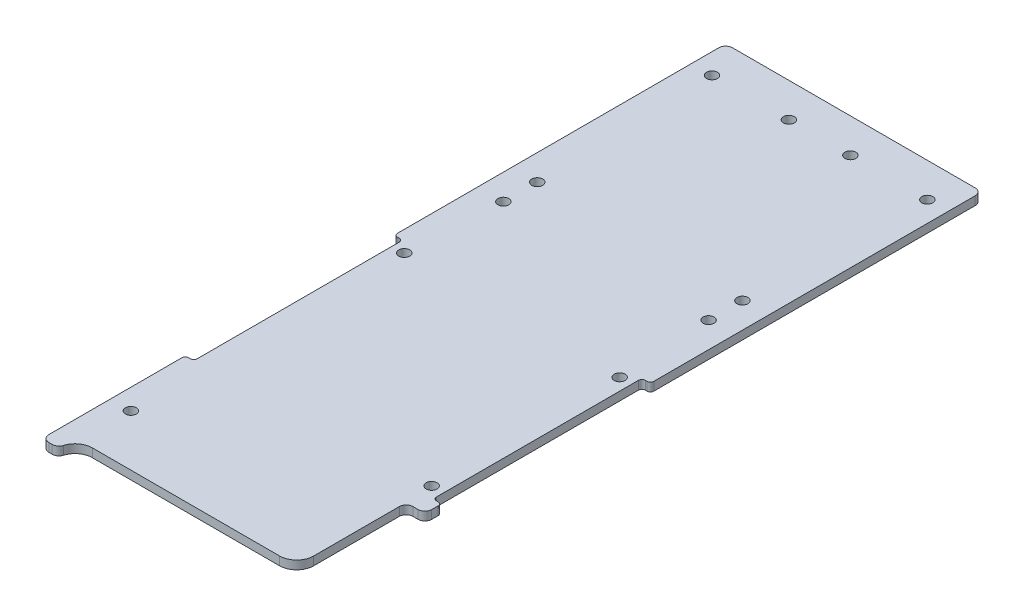
SolidWorks part; units mm, degrees
ref_plane "Front Plane" through (0, 0, 0) normal (0, 0, 1) x (1, 0, 0)
ref_plane "Top Plane" through (0, 0, 0) normal (0, 1, 0) x (1, 0, 0)
ref_plane "Right Plane" through (0, 0, 0) normal (1, 0, 0) x (0, 0, -1)
sketch "Sketch1" plane through (0, 0, 0) normal (0, 1, 0) x (1, 0, 0)
  line L0 (-39.9997, 0) -> (-39.9997, 114.3) construction
  line L1 (-47.625, 127) -> (47.625, 127)
  line L2 (-47.625, 127) -> (-47.625, -127)
  line L3 (-47.625, -127) -> (47.625, -127)
  line L4 (47.625, 127) -> (47.625, -127)
  line L5 (-47.625, 127) -> (47.625, -127) construction
  line L6 (-47.625, -127) -> (47.625, 127) construction
  line L7 (0, 0) -> (0, 127) construction
  line L8 (-39.9997, 0) -> (-39.9997, -101.6) construction
  line L9 (-39.9997, 0) -> (0, 0) construction
  line L10 (-41.275, -127) -> (-41.275, -120.65)
  line L11 (-41.275, -120.65) -> (41.275, -120.65)
  line L12 (41.275, -120.65) -> (41.275, -127)
  line L13 (-39.9997, 114.3) -> (-11.4247, 114.3) construction
  line L14 (39.9997, 114.3) -> (11.4247, 114.3) construction
  circle A0 centre (-39.9997, 114.3) radius 2.032
  circle A1 centre (-39.9997, 0) radius 2.032
  circle A2 centre (-39.9997, -101.6) radius 2.032
  circle A3 centre (39.9997, -101.6) radius 2.032
  circle A4 centre (39.9997, 0) radius 2.032
  circle A5 centre (39.9997, 114.3) radius 2.032
  circle A6 centre (-11.4247, 114.3) radius 2.032
  circle A7 centre (11.4247, 114.3) radius 2.032
  circle A8 centre (-39.9997, -69.85) radius 2.032
  circle A9 centre (39.9997, -69.85) radius 2.032
  point P0 (0, 0)
  dimension "D4" = 4.064
  dimension "D10" = 28.575
  dimension "D1" = 95.25
  dimension "D2" = 254
  dimension "D3" = 7.6253
  dimension "D5" = 12.7
  dimension "D6" = 25.4
  dimension "D7" = 6.35
  dimension "D8" = 6.35
  dimension "D9" = 6.35
  dimension "D11" = 69.85
extrude "Boss-Extrude1" add sketch "Sketch1" along normal blind 3.175 contours L4 L1 L2 L3 A4 A0 A1 A2 A3 A5 | A8 | A3 region at (0, 0, -2.6944) region at (39.9997, 0, 101.6) region at (-39.9997, 0, 69.85)
fillet "Fillet1" radius 2.54 4 edges at (-47.625, 1.5875, -127) (47.625, 1.5875, -127) (47.625, 1.5875, 127) (-47.625, 1.5875, 127)
fillet "Fillet2" radius 2.54 2 edges at (41.275, 1.5875, 127) (-41.275, 1.5875, 127)
fillet "Fillet3" radius 6.35 2 edges at (41.275, 1.5875, 120.65) (-41.275, 1.5875, 120.65)
sketch "Sketch2" plane through (0, 0, 0) normal (0, -1, 0) x (1, 0, 0)
  line L0 (41.9113, 131.8831) -> (41.9113, 109.8659) construction
  line L1 (41.9113, 109.8659) -> (41.9113, 106.3879) construction
  line L2 (41.9113, 83.271) -> (41.9113, 82.5325) construction
  line L3 (41.9113, 82.5325) -> (41.9113, 81.2514) construction
  line L4 (41.9113, 83.271) -> (41.9113, 106.3879) construction
  line L5 (41.9113, 131.8831) -> (41.9113, 109.8659)
  line L6 (41.9113, 109.8659) -> (41.9113, 106.3879)
  line L7 (41.9113, 83.271) -> (41.9113, 82.5325)
  line L8 (41.9113, 82.5325) -> (41.9113, 81.2514)
  line L9 (41.9113, 83.271) -> (41.9113, 106.3879)
  line L10 (41.9113, 81.2514) -> (47.625, 81.2514)
  line L11 (47.625, -124.46) -> (47.625, 124.46) construction
  line L12 (41.9113, 131.8831) -> (47.625, 131.8831)
  line L13 (47.625, 131.8831) -> (47.625, 81.2514)
  line L14 (40.6413, 79.9814) -> (48.895, 79.9814)
  line L15 (48.895, 133.1531) -> (48.895, 79.9814)
  line L16 (40.6413, 133.1531) -> (48.895, 133.1531)
  line L17 (40.6413, 133.1531) -> (40.6413, 109.8659)
  line L18 (40.6413, 109.8659) -> (40.6413, 106.3879)
  line L19 (40.6413, 83.271) -> (40.6413, 106.3879)
  line L20 (40.6413, 83.271) -> (40.6413, 82.5325)
  line L21 (40.6413, 82.5325) -> (40.6413, 79.9814)
  arc M7 (43.815, 127) -> (41.3809, 125.1857) centre (43.815, 124.46) ccw
  arc M8 (41.3809, 125.1857) -> (35.2956, 120.65) centre (35.2956, 127) cw
  line M18 (47.625, -124.46) -> (47.625, 124.46)
  dimension "D1" = 1.27
extrude "Cut-Extrude1" cut sketch "Sketch2" against normal through all contours L20 L21 L14 L10 L8 L7 L9 L19 M18 | L19 L9 L6 L5 L17 L18 M7 M8 | L13 L10 L8 L7 L9 L6 L5 L12 region at (41.6763, 0, 99.9805)
fillet "Fillet4" radius 6.35 1 edges at (40.6413, 1.5875, 123.5728)
fillet "Fillet5" radius 2.54 2 edges at (47.625, 1.5875, 79.9814) (40.6413, 1.5875, 79.9814)
sketch "Sketch3" plane through (0, 0, 0) normal (0, -1, 0) x (1, 0, 0)
  line L0 (-36.3092, -49.7791) -> (-39.916, -49.7791) construction
  line L1 (-40.424, -49.276) -> (-40.424, -45.7043) construction
  line L2 (-35.8012, -45.7043) -> (-35.8012, -49.276) construction
  line L3 (-39.916, -45.2013) -> (-36.3092, -45.2013) construction
  line L4 (-36.3092, -37.2027) -> (-39.916, -37.2027) construction
  line L5 (-35.8012, -33.1279) -> (-35.8012, -36.6996) construction
  line L6 (-40.424, -36.6996) -> (-40.424, -33.1279) construction
  line L7 (-39.916, -32.6249) -> (-36.3092, -32.6249) construction
  line L8 (36.284, -32.6249) -> (39.8908, -32.6249) construction
  line L9 (40.3988, -33.1279) -> (40.3988, -36.6996) construction
  line L10 (39.8908, -37.2027) -> (36.284, -37.2027) construction
  line L11 (35.776, -36.6996) -> (35.776, -33.1279) construction
  line L12 (36.284, -45.2013) -> (39.8908, -45.2013) construction
  line L13 (35.776, -49.276) -> (35.776, -45.7043) construction
  line L14 (40.3988, -45.7043) -> (40.3988, -49.276) construction
  line L15 (39.8908, -49.7791) -> (36.284, -49.7791) construction
  line L16 (-36.3092, -49.7791) -> (-39.916, -49.7791)
  line L17 (-40.424, -49.276) -> (-40.424, -45.7043)
  line L18 (-35.8012, -45.7043) -> (-35.8012, -49.276)
  line L19 (-39.916, -45.2013) -> (-36.3092, -45.2013)
  line L20 (-36.3092, -37.2027) -> (-39.916, -37.2027)
  line L21 (-35.8012, -33.1279) -> (-35.8012, -36.6996)
  line L22 (-40.424, -36.6996) -> (-40.424, -33.1279)
  line L23 (-39.916, -32.6249) -> (-36.3092, -32.6249)
  line L24 (36.284, -32.6249) -> (39.8908, -32.6249)
  line L25 (40.3988, -33.1279) -> (40.3988, -36.6996)
  line L26 (39.8908, -37.2027) -> (36.284, -37.2027)
  line L27 (35.776, -36.6996) -> (35.776, -33.1279)
  line L28 (36.284, -45.2013) -> (39.8908, -45.2013)
  line L29 (35.776, -49.276) -> (35.776, -45.7043)
  line L30 (40.3988, -45.7043) -> (40.3988, -49.276)
  line L31 (39.8908, -49.7791) -> (36.284, -49.7791)
  line L32 (-47.625, -25.836) -> (47.625, -25.836)
  line L33 (-47.625, -124.46) -> (-47.625, 124.46) construction
  line L34 (47.625, -124.46) -> (47.625, 77.4414) construction
  line L35 (0, -25.836) -> (0, -56.0686) construction
  line L38 (134.3616, -51.414) -> (184.1374, -51.414)
  line L39 (184.1374, -51.414) -> (184.1374, -43.4909)
  line L40 (184.1374, -43.4909) -> (182.334, -43.4909)
  line L41 (181.826, -42.9878) -> (181.826, -39.4161)
  line L42 (182.334, -38.9131) -> (184.1374, -38.9131)
  line L43 (184.1374, -38.9131) -> (184.1374, -30.9899)
  line L44 (184.1374, -30.9899) -> (134.3616, -30.9899)
  line L45 (134.3616, -30.9899) -> (133.3374, -32.0042)
  line L46 (133.3374, -32.0042) -> (132.3132, -30.9899)
  line L47 (132.3132, -30.9899) -> (70.8616, -30.9899)
  line L48 (70.8616, -30.9899) -> (69.8374, -32.0042)
  line L49 (69.8374, -32.0042) -> (68.8132, -30.9899)
  line L50 (68.8132, -30.9899) -> (7.3616, -30.9899)
  line L51 (7.3616, -30.9899) -> (6.3374, -32.0042)
  line L52 (6.3374, -32.0042) -> (5.3132, -30.9899)
  line L53 (5.3132, -30.9899) -> (-56.1384, -30.9899)
  line L54 (-56.1384, -30.9899) -> (-57.1626, -32.0042)
  line L55 (-57.1626, -32.0042) -> (-58.1868, -30.9899)
  line L56 (-58.1868, -30.9899) -> (-119.6384, -30.9899)
  line L57 (-119.6384, -30.9899) -> (-120.6626, -32.0042)
  line L58 (-120.6626, -32.0042) -> (-121.6868, -30.9899)
  line L59 (-121.6868, -30.9899) -> (-184.1626, -30.9899)
  line L60 (-184.1626, -30.9899) -> (-184.1626, -51.414)
  line L61 (-184.1626, -51.414) -> (-121.6868, -51.414)
  line L62 (-121.6868, -51.414) -> (-120.6626, -50.3998)
  line L63 (-120.6626, -50.3998) -> (-119.6384, -51.414)
  line L64 (-119.6384, -51.414) -> (-58.1868, -51.414)
  line L65 (-58.1868, -51.414) -> (-57.1626, -50.3998)
  line L66 (-57.1626, -50.3998) -> (-56.1384, -51.414)
  line L67 (-56.1384, -51.414) -> (5.3132, -51.414)
  line L68 (5.3132, -51.414) -> (6.3374, -50.3998)
  line L69 (6.3374, -50.3998) -> (7.3616, -51.414)
  line L70 (7.3616, -51.414) -> (68.8132, -51.414)
  line L71 (68.8132, -51.414) -> (69.8374, -50.3998)
  line L72 (69.8374, -50.3998) -> (70.8616, -51.414)
  line L73 (70.8616, -51.414) -> (132.3132, -51.414)
  line L74 (132.3132, -51.414) -> (133.3374, -50.3998)
  line L75 (133.3374, -50.3998) -> (134.3616, -51.414)
  line L76 (134.3616, -51.414) -> (184.1374, -51.414)
  line L77 (184.1374, -51.414) -> (184.1374, -43.4909)
  line L78 (184.1374, -43.4909) -> (182.334, -43.4909)
  line L79 (181.826, -42.9878) -> (181.826, -39.4161)
  line L80 (182.334, -38.9131) -> (184.1374, -38.9131)
  line L81 (184.1374, -38.9131) -> (184.1374, -30.9899)
  line L82 (184.1374, -30.9899) -> (134.3616, -30.9899)
  line L83 (134.3616, -30.9899) -> (133.3374, -32.0042)
  line L84 (133.3374, -32.0042) -> (132.3132, -30.9899)
  line L85 (132.3132, -30.9899) -> (70.8616, -30.9899)
  line L86 (70.8616, -30.9899) -> (69.8374, -32.0042)
  line L87 (69.8374, -32.0042) -> (68.8132, -30.9899)
  line L88 (68.8132, -30.9899) -> (7.3616, -30.9899)
  line L89 (7.3616, -30.9899) -> (6.3374, -32.0042)
  line L90 (6.3374, -32.0042) -> (5.3132, -30.9899)
  line L91 (5.3132, -30.9899) -> (-56.1384, -30.9899)
  line L92 (-56.1384, -30.9899) -> (-57.1626, -32.0042)
  line L93 (-57.1626, -32.0042) -> (-58.1868, -30.9899)
  line L94 (-58.1868, -30.9899) -> (-119.6384, -30.9899)
  line L95 (-119.6384, -30.9899) -> (-120.6626, -32.0042)
  line L96 (-120.6626, -32.0042) -> (-121.6868, -30.9899)
  line L97 (-121.6868, -30.9899) -> (-184.1626, -30.9899)
  line L98 (-184.1626, -30.9899) -> (-184.1626, -51.414)
  line L99 (-184.1626, -51.414) -> (-121.6868, -51.414)
  line L100 (-121.6868, -51.414) -> (-120.6626, -50.3998)
  line L101 (-120.6626, -50.3998) -> (-119.6384, -51.414)
  line L102 (-119.6384, -51.414) -> (-58.1868, -51.414)
  line L103 (-58.1868, -51.414) -> (-57.1626, -50.3998)
  line L104 (-57.1626, -50.3998) -> (-56.1384, -51.414)
  line L105 (-56.1384, -51.414) -> (5.3132, -51.414)
  line L106 (5.3132, -51.414) -> (6.3374, -50.3998)
  line L107 (6.3374, -50.3998) -> (7.3616, -51.414)
  line L108 (7.3616, -51.414) -> (68.8132, -51.414)
  line L109 (68.8132, -51.414) -> (69.8374, -50.3998)
  line L110 (69.8374, -50.3998) -> (70.8616, -51.414)
  line L111 (70.8616, -51.414) -> (132.3132, -51.414)
  line L112 (132.3132, -51.414) -> (133.3374, -50.3998)
  line L113 (133.3374, -50.3998) -> (134.3616, -51.414)
  line L1362 (-40.424, -34.9138) -> (-35.8012, -34.9138)
  line L1857 (-38.1126, -32.6249) -> (-38.1126, -37.2027)
  line L1858 (-38.1126, -45.2013) -> (-38.1126, -49.7791)
  line L1859 (-40.424, -47.4902) -> (-35.8012, -47.4902)
  circle A0 centre (-38.1126, -34.9138) radius 2.032
  circle A1 centre (-38.1126, -47.4902) radius 2.032
  circle A2 centre (38.1126, -47.4902) radius 2.032
  circle A3 centre (38.1126, -34.9138) radius 2.032
  ellipse E0 centre (-39.916, -45.7043) end of major axis (-39.408, -45.7043) minor radius 0.5031 (-39.916, -45.2013) -> (-40.424, -45.7043) ccw construction
  ellipse E1 centre (-39.916, -49.276) end of major axis (-39.408, -49.276) minor radius 0.5031 (-40.424, -49.276) -> (-39.916, -49.7791) ccw construction
  ellipse E2 centre (182.334, -42.9878) end of major axis (182.842, -42.9878) minor radius 0.5031 (181.826, -42.9878) -> (182.334, -43.4909) ccw
  ellipse E3 centre (182.334, -39.4161) end of major axis (182.842, -39.4161) minor radius 0.5031 (182.334, -38.9131) -> (181.826, -39.4161) ccw
  ellipse E4 centre (182.334, -42.9878) end of major axis (182.842, -42.9878) minor radius 0.5031 (181.826, -42.9878) -> (182.334, -43.4909) ccw
  ellipse E5 centre (182.334, -39.4161) end of major axis (182.842, -39.4161) minor radius 0.5031 (182.334, -38.9131) -> (181.826, -39.4161) ccw
  ellipse E6 centre (-36.3092, -49.276) end of major axis (-35.8012, -49.276) minor radius 0.5031 (-36.3092, -49.7791) -> (-35.8012, -49.276) ccw construction
  ellipse E7 centre (-36.3092, -45.7043) end of major axis (-35.8012, -45.7043) minor radius 0.5031 (-35.8012, -45.7043) -> (-36.3092, -45.2013) ccw construction
  ellipse E8 centre (-39.916, -36.6996) end of major axis (-39.408, -36.6996) minor radius 0.5031 (-40.424, -36.6996) -> (-39.916, -37.2027) ccw construction
  ellipse E9 centre (-36.3092, -36.6996) end of major axis (-35.8012, -36.6996) minor radius 0.5031 (-36.3092, -37.2027) -> (-35.8012, -36.6996) ccw construction
  ellipse E10 centre (-36.3092, -33.1279) end of major axis (-35.8012, -33.1279) minor radius 0.5031 (-35.8012, -33.1279) -> (-36.3092, -32.6249) ccw construction
  ellipse E11 centre (-39.916, -33.1279) end of major axis (-39.408, -33.1279) minor radius 0.5031 (-39.916, -32.6249) -> (-40.424, -33.1279) ccw construction
  ellipse E12 centre (39.8908, -33.1279) end of major axis (40.3988, -33.1279) minor radius 0.5031 (40.3988, -33.1279) -> (39.8908, -32.6249) ccw construction
  ellipse E13 centre (36.284, -33.1279) end of major axis (36.792, -33.1279) minor radius 0.5031 (36.284, -32.6249) -> (35.776, -33.1279) ccw construction
  ellipse E14 centre (39.8908, -36.6996) end of major axis (40.3988, -36.6996) minor radius 0.5031 (39.8908, -37.2027) -> (40.3988, -36.6996) ccw construction
  ellipse E15 centre (36.284, -36.6996) end of major axis (36.792, -36.6996) minor radius 0.5031 (35.776, -36.6996) -> (36.284, -37.2027) ccw construction
  ellipse E16 centre (36.284, -45.7043) end of major axis (36.792, -45.7043) minor radius 0.5031 (36.284, -45.2013) -> (35.776, -45.7043) ccw construction
  ellipse E17 centre (36.284, -49.276) end of major axis (36.792, -49.276) minor radius 0.5031 (35.776, -49.276) -> (36.284, -49.7791) ccw construction
  ellipse E18 centre (39.8908, -45.7043) end of major axis (40.3988, -45.7043) minor radius 0.5031 (40.3988, -45.7043) -> (39.8908, -45.2013) ccw construction
  ellipse E19 centre (39.8908, -49.276) end of major axis (40.3988, -49.276) minor radius 0.5031 (39.8908, -49.7791) -> (40.3988, -49.276) ccw construction
  ellipse E20 centre (-39.916, -45.7043) end of major axis (-39.408, -45.7043) minor radius 0.5031 (-39.916, -45.2013) -> (-40.424, -45.7043) ccw
  ellipse E21 centre (-39.916, -49.276) end of major axis (-39.408, -49.276) minor radius 0.5031 (-40.424, -49.276) -> (-39.916, -49.7791) ccw
  ellipse E22 centre (-36.3092, -49.276) end of major axis (-35.8012, -49.276) minor radius 0.5031 (-36.3092, -49.7791) -> (-35.8012, -49.276) ccw
  ellipse E23 centre (-36.3092, -45.7043) end of major axis (-35.8012, -45.7043) minor radius 0.5031 (-35.8012, -45.7043) -> (-36.3092, -45.2013) ccw
  ellipse E24 centre (-39.916, -36.6996) end of major axis (-39.408, -36.6996) minor radius 0.5031 (-40.424, -36.6996) -> (-39.916, -37.2027) ccw
  ellipse E25 centre (-36.3092, -36.6996) end of major axis (-35.8012, -36.6996) minor radius 0.5031 (-36.3092, -37.2027) -> (-35.8012, -36.6996) ccw
  ellipse E26 centre (-36.3092, -33.1279) end of major axis (-35.8012, -33.1279) minor radius 0.5031 (-35.8012, -33.1279) -> (-36.3092, -32.6249) ccw
  ellipse E27 centre (-39.916, -33.1279) end of major axis (-39.408, -33.1279) minor radius 0.5031 (-39.916, -32.6249) -> (-40.424, -33.1279) ccw
  ellipse E28 centre (39.8908, -33.1279) end of major axis (40.3988, -33.1279) minor radius 0.5031 (40.3988, -33.1279) -> (39.8908, -32.6249) ccw
  ellipse E29 centre (36.284, -33.1279) end of major axis (36.792, -33.1279) minor radius 0.5031 (36.284, -32.6249) -> (35.776, -33.1279) ccw
  ellipse E30 centre (39.8908, -36.6996) end of major axis (40.3988, -36.6996) minor radius 0.5031 (39.8908, -37.2027) -> (40.3988, -36.6996) ccw
  ellipse E31 centre (36.284, -36.6996) end of major axis (36.792, -36.6996) minor radius 0.5031 (35.776, -36.6996) -> (36.284, -37.2027) ccw
  ellipse E32 centre (36.284, -45.7043) end of major axis (36.792, -45.7043) minor radius 0.5031 (36.284, -45.2013) -> (35.776, -45.7043) ccw
  ellipse E33 centre (36.284, -49.276) end of major axis (36.792, -49.276) minor radius 0.5031 (35.776, -49.276) -> (36.284, -49.7791) ccw
  ellipse E34 centre (39.8908, -45.7043) end of major axis (40.3988, -45.7043) minor radius 0.5031 (40.3988, -45.7043) -> (39.8908, -45.2013) ccw
  ellipse E35 centre (39.8908, -49.276) end of major axis (40.3988, -49.276) minor radius 0.5031 (39.8908, -49.7791) -> (40.3988, -49.276) ccw
  dimension "D2" = 4.064
  dimension "D1" = 0
extrude "Cut-Extrude2" cut sketch "Sketch3" against normal through all contours A0 | A1 | A2 | A3
sketch "Sketch4" plane through (0, 3.175, 0) normal (0, 1, 0) x (1, 0, 0)
  line L0 (-44.45, 3.81) -> (-46.99, 3.81) construction
  line L1 (-46.99, 3.81) -> (-46.99, 121.92) construction
  line L2 (-42.545, 126.365) -> (-0.635, 126.365) construction
  line L3 (-0.635, 126.365) -> (-0.635, 107.95) construction
  line L4 (-6.35, 102.235) -> (-15.875, 102.235) construction
  line L5 (-22.86, 95.25) -> (-22.86, -115.57) construction
  line L6 (-27.305, -120.015) -> (-35.4551, -120.015) construction
  line L7 (-43.815, -126.365) -> (-45.085, -126.365) construction
  line L8 (-46.99, -124.46) -> (-46.99, -73.7819) construction
  line L9 (-46.99, -73.7819) -> (-44.45, -73.7819) construction
  line L10 (-44.45, -73.7819) -> (-44.45, 3.81) construction
  line L11 (-46.99, 3.81) -> (-44.45, 3.81)
  line L12 (-46.99, 121.92) -> (-46.99, 3.81)
  line L13 (-0.635, 126.365) -> (-42.545, 126.365)
  line L14 (-0.635, 107.95) -> (-0.635, 126.365)
  line L15 (-15.875, 102.235) -> (-6.35, 102.235)
  line L16 (-22.86, -115.57) -> (-22.86, 95.25)
  line L17 (-35.4551, -120.015) -> (-27.305, -120.015)
  line L18 (-45.085, -126.365) -> (-43.815, -126.365)
  line L19 (-46.99, -73.7819) -> (-46.99, -124.46)
  line L20 (-44.45, -73.7819) -> (-46.99, -73.7819)
  line L21 (-44.45, 3.81) -> (-44.45, -73.7819)
  line L22 (-46.99, 3.81) -> (-44.45, 3.81)
  line L23 (-46.99, 121.92) -> (-46.99, 3.81)
  line L24 (-0.635, 126.365) -> (-42.545, 126.365)
  line L25 (-0.635, 107.95) -> (-0.635, 126.365)
  line L26 (-15.875, 102.235) -> (-6.35, 102.235)
  line L27 (-22.86, -115.57) -> (-22.86, 95.25)
  line L28 (-35.4551, -120.015) -> (-27.305, -120.015)
  line L29 (-45.085, -126.365) -> (-43.815, -126.365)
  line L30 (-46.99, -73.7819) -> (-46.99, -124.46)
  line L31 (-44.45, -73.7819) -> (-46.99, -73.7819)
  line L32 (-44.45, 3.81) -> (-44.45, -73.7819)
  line L33 (40.64, -77.5286) -> (40.64, -117.0408) construction
  line L34 (35.4551, -120.015) -> (27.305, -120.015) construction
  line L35 (22.86, -115.57) -> (22.86, 95.25) construction
  line L36 (15.875, 102.235) -> (6.35, 102.235) construction
  line L37 (0.635, 107.95) -> (0.635, 126.365) construction
  line L38 (0.635, 126.365) -> (42.545, 126.365) construction
  line L39 (46.99, 121.92) -> (46.99, 3.81) construction
  line L40 (46.99, 3.81) -> (44.45, 3.81) construction
  line L41 (44.45, 3.81) -> (44.45, -73.7819) construction
  line L42 (44.45, -73.7819) -> (46.99, -73.7819) construction
  line L43 (46.99, -73.7819) -> (46.99, -77.5286) construction
  line L44 (46.99, -77.5286) -> (40.64, -77.5286) construction
  line L45 (-44.45, 3.81) -> (-46.99, 3.81)
  line L46 (-46.99, 3.81) -> (-46.99, 121.92)
  line L47 (-42.545, 126.365) -> (-0.635, 126.365)
  line L48 (-0.635, 126.365) -> (-0.635, 107.95)
  line L49 (-6.35, 102.235) -> (-15.875, 102.235)
  line L50 (-22.86, 95.25) -> (-22.86, -115.57)
  line L51 (-27.305, -120.015) -> (-35.4551, -120.015)
  line L52 (-43.815, -126.365) -> (-45.085, -126.365)
  line L53 (-46.99, -124.46) -> (-46.99, -73.7819)
  line L54 (-46.99, -73.7819) -> (-44.45, -73.7819)
  line L55 (-44.45, -73.7819) -> (-44.45, 3.81)
  line L56 (40.64, -77.5286) -> (40.64, -117.0408)
  line L57 (35.4551, -120.015) -> (27.305, -120.015)
  line L58 (22.86, -115.57) -> (22.86, 95.25)
  line L59 (15.875, 102.235) -> (6.35, 102.235)
  line L60 (0.635, 107.95) -> (0.635, 126.365)
  line L61 (0.635, 126.365) -> (42.545, 126.365)
  line L62 (46.99, 121.92) -> (46.99, 3.81)
  line L63 (46.99, 3.81) -> (44.45, 3.81)
  line L64 (44.45, 3.81) -> (44.45, -73.7819)
  line L65 (44.45, -73.7819) -> (46.99, -73.7819)
  line L66 (46.99, -73.7819) -> (46.99, -77.5286)
  line L67 (46.99, -77.5286) -> (40.64, -77.5286)
  line L178 (-46.99, 3.81) -> (-47.625, 3.81)
  line L179 (-47.625, 124.46) -> (-47.625, -124.46) construction
  line L180 (-46.99, -73.7819) -> (-47.625, -73.7819)
  line L181 (46.99, -73.7819) -> (47.625, -73.7819)
  line L182 (47.625, 124.46) -> (47.625, -77.4414) construction
  line L183 (46.99, 3.81) -> (47.625, 3.81)
  arc A0 (-42.545, 126.365) -> (-46.99, 121.92) centre (-42.545, 121.92) ccw construction
  arc A1 (-6.35, 102.235) -> (-0.635, 107.95) centre (-6.35, 107.95) ccw construction
  arc A2 (-15.875, 102.235) -> (-22.86, 95.25) centre (-15.875, 95.25) ccw construction
  arc A3 (-27.305, -120.015) -> (-22.86, -115.57) centre (-27.305, -115.57) ccw construction
  arc A4 (-35.4551, -120.015) -> (-41.9138, -124.3399) centre (-35.4551, -127) ccw construction
  arc A5 (-43.815, -126.365) -> (-41.9138, -124.3399) centre (-43.815, -124.46) ccw construction
  arc A6 (-46.99, -124.46) -> (-45.085, -126.365) centre (-45.085, -124.46) ccw construction
  arc A7 (-42.545, 126.365) -> (-46.99, 121.92) centre (-42.545, 121.92) ccw
  arc A8 (-6.35, 102.235) -> (-0.635, 107.95) centre (-6.35, 107.95) ccw
  arc A9 (-15.875, 102.235) -> (-22.86, 95.25) centre (-15.875, 95.25) ccw
  arc A10 (-27.305, -120.015) -> (-22.86, -115.57) centre (-27.305, -115.57) ccw
  arc A11 (-35.4551, -120.015) -> (-41.9138, -124.3399) centre (-35.4551, -127) ccw
  arc A12 (-43.815, -126.365) -> (-41.9138, -124.3399) centre (-43.815, -124.46) ccw
  arc A13 (-46.99, -124.46) -> (-45.085, -126.365) centre (-45.085, -124.46) ccw
  arc A14 (-42.545, 126.365) -> (-46.99, 121.92) centre (-42.545, 121.92) ccw
  arc A15 (-6.35, 102.235) -> (-0.635, 107.95) centre (-6.35, 107.95) ccw
  arc A16 (-15.875, 102.235) -> (-22.86, 95.25) centre (-15.875, 95.25) ccw
  arc A17 (-27.305, -120.015) -> (-22.86, -115.57) centre (-27.305, -115.57) ccw
  arc A18 (-35.4551, -120.015) -> (-41.9138, -124.3399) centre (-35.4551, -127) ccw
  arc A19 (-43.815, -126.365) -> (-41.9138, -124.3399) centre (-43.815, -124.46) ccw
  arc A20 (-46.99, -124.46) -> (-45.085, -126.365) centre (-45.085, -124.46) ccw
  arc A21 (36.8369, -120.153) -> (40.64, -117.0408) centre (37.465, -117.0408) ccw construction
  arc A22 (36.8369, -120.153) -> (35.4551, -120.015) centre (35.4551, -127) ccw construction
  arc A23 (22.86, -115.57) -> (27.305, -120.015) centre (27.305, -115.57) ccw construction
  arc A24 (22.86, 95.25) -> (15.875, 102.235) centre (15.875, 95.25) ccw construction
  arc A25 (0.635, 107.95) -> (6.35, 102.235) centre (6.35, 107.95) ccw construction
  arc A26 (46.99, 121.92) -> (42.545, 126.365) centre (42.545, 121.92) ccw construction
  arc A27 (-42.545, 126.365) -> (-46.99, 121.92) centre (-42.545, 121.92) ccw
  arc A28 (-6.35, 102.235) -> (-0.635, 107.95) centre (-6.35, 107.95) ccw
  arc A29 (-15.875, 102.235) -> (-22.86, 95.25) centre (-15.875, 95.25) ccw
  arc A30 (-27.305, -120.015) -> (-22.86, -115.57) centre (-27.305, -115.57) ccw
  arc A31 (-35.4551, -120.015) -> (-41.9138, -124.3399) centre (-35.4551, -127) ccw
  arc A32 (-43.815, -126.365) -> (-41.9138, -124.3399) centre (-43.815, -124.46) ccw
  arc A33 (-46.99, -124.46) -> (-45.085, -126.365) centre (-45.085, -124.46) ccw
  arc A34 (36.8369, -120.153) -> (40.64, -117.0408) centre (37.465, -117.0408) ccw
  arc A35 (36.8369, -120.153) -> (35.4551, -120.015) centre (35.4551, -127) ccw
  arc A36 (22.86, -115.57) -> (27.305, -120.015) centre (27.305, -115.57) ccw
  arc A37 (22.86, 95.25) -> (15.875, 102.235) centre (15.875, 95.25) ccw
  arc A38 (0.635, 107.95) -> (6.35, 102.235) centre (6.35, 107.95) ccw
  arc A39 (46.99, 121.92) -> (42.545, 126.365) centre (42.545, 121.92) ccw
  line M32 (47.625, -77.4414) -> (47.625, 124.46)
  line M36 (-47.625, 124.46) -> (-47.625, -124.46)
  dimension "D1" = 0
extrude "Cut-Extrude3" cut sketch "Sketch4" against normal through all and the other way through all contours L180 L31 L32 L22 L178 M36 | L183 L63 L64 L65 L181 M32 region at (-46.0375, 3.175, 34.9859) region at (46.0375, 3.175, 34.9859)
fillet "Fillet6" radius 1.27 8 edges at (-44.45, 1.5875, -3.81) (-44.45, 1.5875, 73.7819) (44.45, 1.5875, -3.81) (44.45, 1.5875, 73.7819) (47.625, 1.5875, 73.7819) (47.625, 1.5875, -3.81) (-47.625, 1.5875, 73.7819) (-47.625, 1.5875, -3.81)
